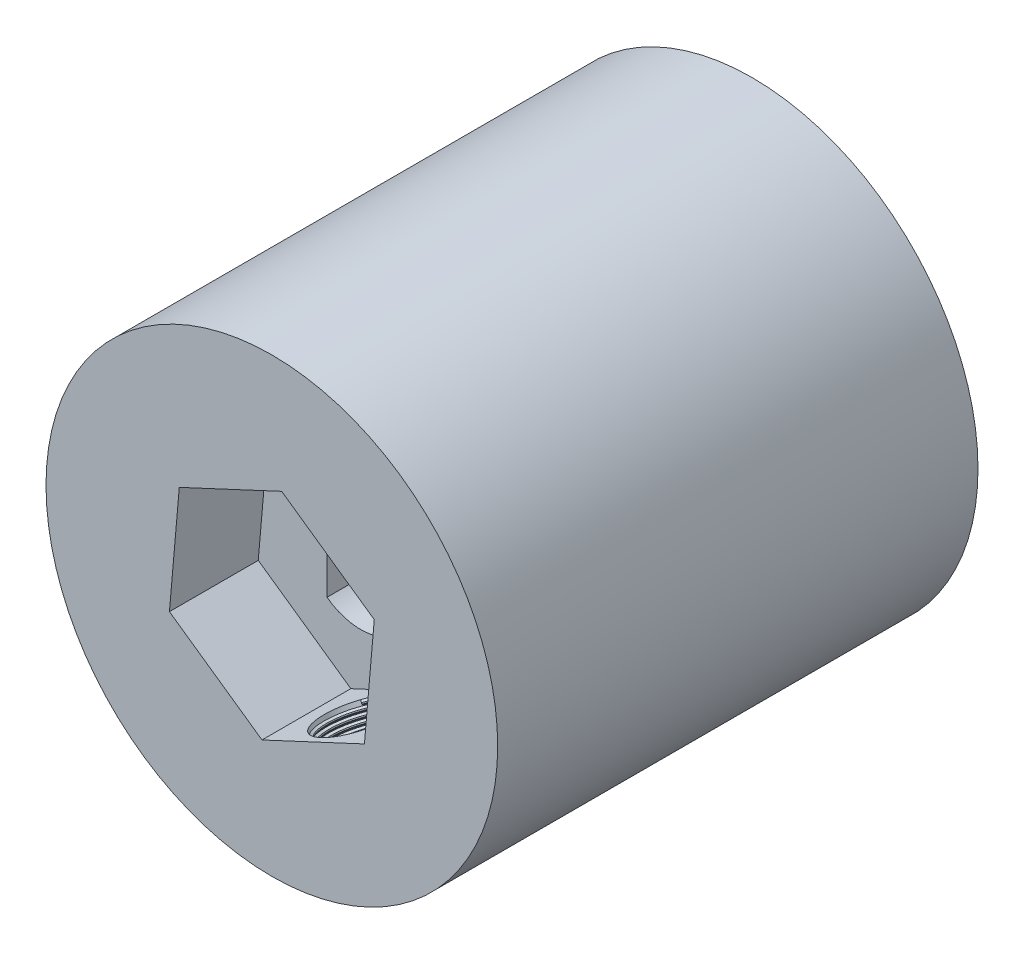
SolidWorks part; units mm, degrees
ref_plane "Front Plane" through (0, 0, 0) normal (0, 0, 1) x (1, 0, 0)
ref_plane "Top Plane" through (0, 0, 0) normal (0, 1, 0) x (1, 0, 0)
ref_plane "Right Plane" through (0, 0, 0) normal (1, 0, 0) x (0, 0, -1)
sketch "Sketch2" plane through (0, 0, 0) normal (0, 0, 1) x (1, 0, 0)
  line L12 (-0.6542, -7.477) -> (6.1482, -4.305)
  line L13 (6.1482, -4.305) -> (6.8023, 3.172)
  line L14 (6.8023, 3.172) -> (0.6542, 7.477)
  line L15 (0.6542, 7.477) -> (-6.1482, 4.305)
  line L16 (-6.1482, 4.305) -> (-6.8023, -3.172)
  line L17 (-6.8023, -3.172) -> (-0.6542, -7.477)
  circle A0 centre (0, 0) radius 15
extrude "Boss-Extrude4" add sketch "Sketch2" along normal blind 5.9
sketch "Sketch9" plane through (0, 0, 0) normal (0, 0, 1) x (1, 0, 0)
  line L4 (2.2354, -3.0109) -> (2.2354, 3.0109)
  line L5 (-2.2354, 3.0109) -> (-2.2354, -3.0109)
  circle A0 centre (0, 0) radius 15
  arc A4 (-2.2354, -3.0109) -> (2.2354, -3.0109) centre (0, 0) ccw
  arc A5 (2.2354, 3.0109) -> (-2.2354, 3.0109) centre (0, 0) ccw
extrude "Boss-Extrude5" add sketch "Sketch9" against normal blind 3
sketch "Sketch11" plane through (0, 0, -3) normal (0, 0, -1) x (-1, 0, 0)
  circle A0 centre (0, 0) radius 15
extrude "Boss-Extrude6" add sketch "Sketch11" along normal blind 15
sketch "Sketch33" plane through (0, 0, -18) normal (0, 0, -1) x (-1, 0, 0)
  line L0 (1.5607, 7.8463) -> (1.2643, 6.3562)
  line L1 (-1.2643, 6.3562) -> (-1.5607, 7.8463)
  line L2 (-4.4446, 6.6518) -> (-3.6005, 5.3885)
  line L3 (-5.3885, 3.6005) -> (-6.6518, 4.4446)
  line L4 (-7.8463, 1.5607) -> (-6.3562, 1.2643)
  line L5 (-6.3562, -1.2643) -> (-7.8463, -1.5607)
  line L6 (-6.6518, -4.4446) -> (-5.3885, -3.6005)
  line L7 (-3.6005, -5.3885) -> (-4.4446, -6.6518)
  line L8 (-1.5607, -7.8463) -> (-1.2643, -6.3562)
  line L9 (1.2643, -6.3562) -> (1.5607, -7.8463)
  line L10 (4.4446, -6.6518) -> (3.6005, -5.3885)
  line L11 (5.3885, -3.6005) -> (6.6518, -4.4446)
  line L12 (7.8463, -1.5607) -> (6.3562, -1.2643)
  line L13 (6.3562, 1.2643) -> (7.8463, 1.5607)
  line L14 (6.6518, 4.4446) -> (5.3885, 3.6005)
  line L15 (3.6005, 5.3885) -> (4.4446, 6.6518)
  circle A0 centre (0, 0) radius 15
  arc A1 (4.4446, 6.6518) -> (4.5299, 9.4726) centre (1.841, 8.1423) ccw
  arc A2 (4.5299, 9.4726) -> (3.495, 9.9013) centre (0, 0) ccw
  arc A3 (3.495, 9.9013) -> (1.5607, 7.8463) centre (4.4556, 7.0593) ccw
  arc A4 (0.7144, 5.9573) -> (1.2643, 6.3562) centre (0.7739, 6.4538) ccw
  arc A5 (0.7144, 5.9573) -> (-0.7144, 5.9573) centre (0, 0) ccw
  arc A6 (-1.2643, 6.3562) -> (-0.7144, 5.9573) centre (-0.7739, 6.4538) ccw
  arc A7 (-1.5607, 7.8463) -> (-3.495, 9.9013) centre (-4.4556, 7.0593) ccw
  arc A8 (-3.495, 9.9013) -> (-4.5299, 9.4726) centre (0, 0) ccw
  arc A9 (-4.5299, 9.4726) -> (-4.4446, 6.6518) centre (-1.841, 8.1423) ccw
  arc A10 (-3.7073, 4.7176) -> (-3.6005, 5.3885) centre (-4.0162, 5.1108) ccw
  arc A11 (-3.7073, 4.7176) -> (-4.7176, 3.7073) centre (0, 0) ccw
  arc A12 (-5.3885, 3.6005) -> (-4.7176, 3.7073) centre (-5.1108, 4.0162) ccw
  arc A13 (-6.6518, 4.4446) -> (-9.4726, 4.5299) centre (-8.1423, 1.841) ccw
  arc A14 (-9.4726, 4.5299) -> (-9.9013, 3.495) centre (0, 0) ccw
  arc A15 (-9.9013, 3.495) -> (-7.8463, 1.5607) centre (-7.0593, 4.4556) ccw
  arc A16 (-5.9573, 0.7144) -> (-6.3562, 1.2643) centre (-6.4538, 0.7739) ccw
  arc A17 (-5.9573, 0.7144) -> (-5.9573, -0.7144) centre (0, 0) ccw
  arc A18 (-6.3562, -1.2643) -> (-5.9573, -0.7144) centre (-6.4538, -0.7739) ccw
  arc A19 (-7.8463, -1.5607) -> (-9.9013, -3.495) centre (-7.0593, -4.4556) ccw
  arc A20 (-9.9013, -3.495) -> (-9.4726, -4.5299) centre (0, 0) ccw
  arc A21 (-9.4726, -4.5299) -> (-6.6518, -4.4446) centre (-8.1423, -1.841) ccw
  arc A22 (-4.7176, -3.7073) -> (-5.3885, -3.6005) centre (-5.1108, -4.0162) ccw
  arc A23 (-4.7176, -3.7073) -> (-3.7073, -4.7176) centre (0, 0) ccw
  arc A24 (-3.6005, -5.3885) -> (-3.7073, -4.7176) centre (-4.0162, -5.1108) ccw
  arc A25 (-4.4446, -6.6518) -> (-4.5299, -9.4726) centre (-1.841, -8.1423) ccw
  arc A26 (-4.5299, -9.4726) -> (-3.495, -9.9013) centre (0, 0) ccw
  arc A27 (-3.495, -9.9013) -> (-1.5607, -7.8463) centre (-4.4556, -7.0593) ccw
  arc A28 (-0.7144, -5.9573) -> (-1.2643, -6.3562) centre (-0.7739, -6.4538) ccw
  arc A29 (-0.7144, -5.9573) -> (0.7144, -5.9573) centre (0, 0) ccw
  arc A30 (1.2643, -6.3562) -> (0.7144, -5.9573) centre (0.7739, -6.4538) ccw
  arc A31 (1.5607, -7.8463) -> (3.495, -9.9013) centre (4.4556, -7.0593) ccw
  arc A32 (3.495, -9.9013) -> (4.5299, -9.4726) centre (0, 0) ccw
  arc A33 (4.5299, -9.4726) -> (4.4446, -6.6518) centre (1.841, -8.1423) ccw
  arc A34 (3.7073, -4.7176) -> (3.6005, -5.3885) centre (4.0162, -5.1108) ccw
  arc A35 (3.7073, -4.7176) -> (4.7176, -3.7073) centre (0, 0) ccw
  arc A36 (5.3885, -3.6005) -> (4.7176, -3.7073) centre (5.1108, -4.0162) ccw
  arc A37 (6.6518, -4.4446) -> (9.4726, -4.5299) centre (8.1423, -1.841) ccw
  arc A38 (9.4726, -4.5299) -> (9.9013, -3.495) centre (0, 0) ccw
  arc A39 (9.9013, -3.495) -> (7.8463, -1.5607) centre (7.0593, -4.4556) ccw
  arc A40 (5.9573, -0.7144) -> (6.3562, -1.2643) centre (6.4538, -0.7739) ccw
  arc A41 (5.9573, -0.7144) -> (5.9573, 0.7144) centre (0, 0) ccw
  arc A42 (6.3562, 1.2643) -> (5.9573, 0.7144) centre (6.4538, 0.7739) ccw
  arc A43 (7.8463, 1.5607) -> (9.9013, 3.495) centre (7.0593, 4.4556) ccw
  arc A44 (9.9013, 3.495) -> (9.4726, 4.5299) centre (0, 0) ccw
  arc A45 (9.4726, 4.5299) -> (6.6518, 4.4446) centre (8.1423, 1.841) ccw
  arc A46 (4.7176, 3.7073) -> (5.3885, 3.6005) centre (5.1108, 4.0162) ccw
  arc A47 (4.7176, 3.7073) -> (3.7073, 4.7176) centre (0, 0) ccw
  arc A48 (3.6005, 5.3885) -> (3.7073, 4.7176) centre (4.0162, 5.1108) ccw
extrude "Boss-Extrude10" add sketch "Sketch33" along normal blind 8
sketch "Sketch34" plane through (0, 0, -18) normal (0, 0, -1) x (-1, 0, 0)
  circle A0 centre (0, 0) radius 1
extrude "Boss-Extrude11" add sketch "Sketch34" along normal blind 8
sketch "Sketch36" plane through (2.747, -5.891, 0) normal (-0.4226, 0.9063, 0) x (0.9063, 0.4226, 0)
  circle A0 centre (0, -2.9) radius 2.5
extrude "Cut-Extrude5" cut sketch "Sketch36" against normal blind 10
thread "Thread1" pitch 0.3175 method extrude profile "Thread Profile2" start angle 45, offset 0, length 8.3, pitch 0.3175, diameter 5
ref_plane "Plane3" through (1.1449, -6.6381, 1.1322) normal (-0.6409, -0.2988, 0.7071) x (-0.6409, -0.2988, -0.7071)
sketch "Thread Profile2" plane through (1.1449, -6.6381, 1.1322) normal (-0.6409, -0.2988, 0.7071) x (-0.6409, -0.2988, -0.7071)
  line L0 (0, 0) -> (0, 0.3175) construction
  line L11 (0, 0) -> (0, 0.2778)
  line L12 (0, 0.2778) -> (-0.1719, 0.1786)
  line L13 (-0.1719, 0.1786) -> (-0.1719, 0.0992)
  line L15 (-0.1719, 0.0992) -> (0, 0)
  line L17 (-0.1719, 0.1389) -> (0, 0.1389) construction
  point P2 (0, 0)
  dimension "Pitch" = 0.3175
  dimension "Profile_Angle" = 60
  dimension "Profile_Land" = 0.0794
  dimension "Profile_Height" = 0.1719
ref_point "Point1"
ref_plane "Plane4" through (4.0182, -9.7007, -22) normal (-0.3827, 0.9239, 0) x (0.9239, 0.3827, 0)
sketch "Sketch37" plane through (0, 0, -26) normal (0, 0, -1) x (-1, 0, 0)
  circle A6 centre (0, 0) radius 1 construction
  circle A7 centre (0, 0) radius 1 construction
  point P6 (-1, 0)
  point P7 (1, 0)
  point P8 (0, 0)
  dimension "D3" = 8.9013
  dimension "D2" = 4.9573
  dimension "D1" = 2
equation "\"45degdeg\"=0"
equation "\"45degeg\"=0"
